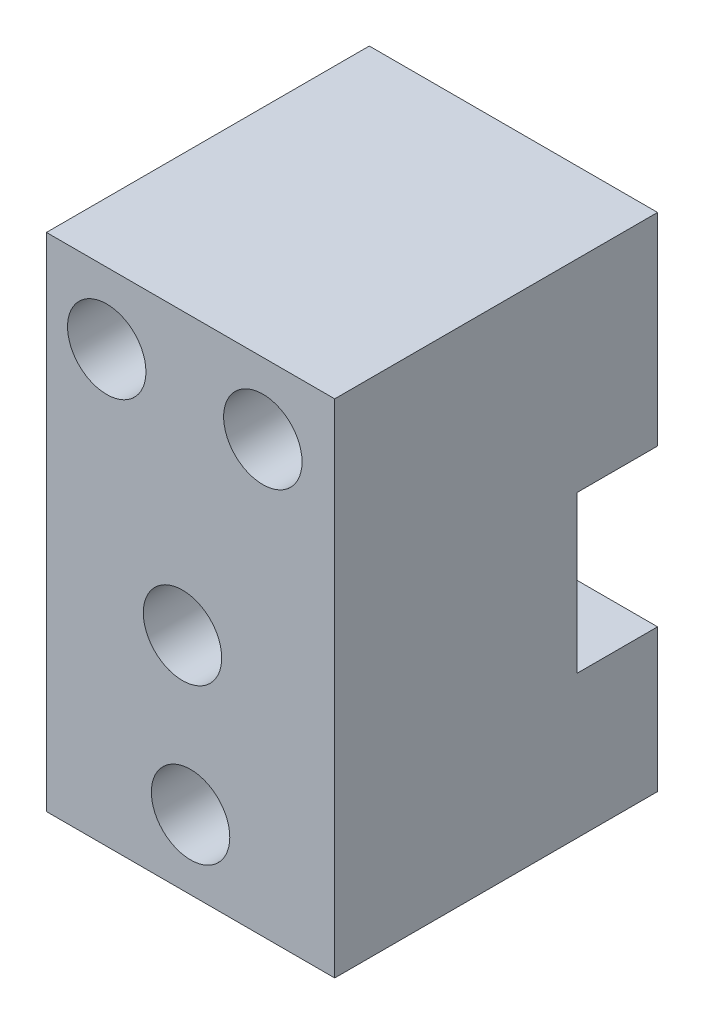
SolidWorks part; units mm, degrees
ref_plane "Plan de face" through (0, 0, 0) normal (0, 0, 1) x (1, 0, 0)
ref_plane "Plan de dessus" through (0, 0, 0) normal (0, 1, 0) x (1, 0, 0)
ref_plane "Plan de droite" through (0, 0, 0) normal (1, 0, 0) x (0, 0, -1)
sketch "Esquisse1" plane through (0, 0, 0) normal (0, 0, 1) x (1, 0, 0)
  line L1 (-6.25, -10.875) -> (6.25, -10.875)
  line L2 (-6.25, -10.875) -> (-6.25, 10.875)
  line L3 (-6.25, 10.875) -> (6.25, 10.875)
  line L4 (6.25, -10.875) -> (6.25, 10.875)
  line L5 (-6.25, -10.875) -> (6.25, 10.875) construction
  line L6 (-6.25, 10.875) -> (6.25, -10.875) construction
  point P0 (0, 0)
  dimension "D1" = 21.75
  dimension "D2" = 12.5
extrude "Boss.-Extru.3" add sketch "Esquisse1" along normal blind 14
sketch "Esquisse9" plane through (0, 0, 14) normal (0, 0, 1) x (1, 0, 0)
  line L0 (-3.6356, -4.6863) -> (-3.6356, 2.1017)
  line L1 (-3.6356, -4.6863) -> (6.9438, -4.6863)
  line L2 (-3.6356, 2.1017) -> (6.9438, 2.1017)
  line L3 (6.9438, -4.6863) -> (6.9438, 2.1017)
extrude "Enlèv. mat.-Extru.7" cut sketch "Esquisse9" against normal blind 3.5
hole_wizard "Dégagement M32" positions "Esquisse17" profile "Esquisse16" hole size "M3" standard "JIS" end condition through all
sketch "Esquisse17" plane through (0, 0, 14) normal (0, 0, 1) x (1, 0, 0)
  point P0 (-0.35, -1.3062)
sketch "Esquisse16" plane through (-0.35, -1.3062, 14) normal (1, 0, 0) x (0, -1, 0)
  line L0 (0, 0) -> (0, 14)
  line L1 (0, 14) -> (1.7, 14)
  line L2 (1.7, 14) -> (1.7, 0)
  line L5 (1.7, 0) -> (0, 0)
  line L11 (0, -6.35) -> (0, 107.95) construction
  dimension "Diamètre du perçage jusqu'au prochain" = 3.4
  dimension "Profondeur du perçage jusqu'au prochain" = 14
hole_wizard "Dégagement M33" positions "Esquisse20" profile "Esquisse18" hole size "M3" standard "JIS" end condition through all
sketch "Esquisse20" plane through (0, 0, 14) normal (0, 0, 1) x (1, 0, 0)
  point P0 (-3.6356, 7.7949)
  point P2 (3.1342, 7.7949)
  point P4 (0, -7.8658)
sketch "Esquisse18" plane through (-3.6356, 7.7949, 14) normal (1, 0, 0) x (0, -1, 0)
  line L0 (0, 0) -> (0, 14)
  line L1 (0, 14) -> (1.7, 14)
  line L2 (1.7, 14) -> (1.7, 0)
  line L5 (1.7, 0) -> (0, 0)
  line L11 (0, -6.35) -> (0, 107.95) construction
  dimension "Diamètre du perçage jusqu'au prochain" = 3.4
  dimension "Profondeur du perçage jusqu'au prochain" = 14
sketch "Esquisse21" plane through (6.25, 0, 0) normal (1, 0, 0) x (0, 0, -1)
  line L0 (-7, 10.875) -> (-7, -10.875) construction
  line L1 (-14, 10.875) -> (0, 10.875) construction
  line L2 (-14, -10.875) -> (0, -10.875) construction
ref_axis "Axe1" through (6.25, 10.875, 7) along (0, -1, 0)
ref_plane "Plan1" through (0, 0, 7) normal (0, 0, 1) x (0, -1, 0)
mirror "Symétrie1" about plane through (0, 0, 7) normal (0, 0, 1) of "Enlèv. mat.-Extru.7"
sketch "Esquisse23" plane through (0, 0, 10.5) normal (0, 0, 1) x (1, 0, 0)
  line L4 (-3.6356, 2.1017) -> (-3.6356, -4.6863)
  line L5 (6.25, 2.1017) -> (6.25, -4.6863)
  line L7 (6.25, -4.6863) -> (-3.6356, -4.6863)
  line L8 (-3.6356, -4.6863) -> (-3.6356, 2.1017)
  line L9 (-3.6356, 2.1017) -> (6.25, 2.1017)
  line L10 (6.25, -4.6863) -> (-3.6356, -4.6863)
  line L11 (-3.6356, -4.6863) -> (-3.6356, 2.1017)
  line L12 (-3.6356, 2.1017) -> (6.25, 2.1017)
  circle M4 centre (-0.35, -1.3062) radius 1.7
  line M5 (6.25, -4.6863) -> (6.25, 2.1017)
  line M6 (6.25, 2.1017) -> (-3.6356, 2.1017)
  line M7 (-3.6356, 2.1017) -> (-3.6356, -4.6863)
  line M8 (-3.6356, -4.6863) -> (6.25, -4.6863)
  dimension "D1" = 0
extrude "Boss.-Extru.4" add sketch "Esquisse23" along normal up to surface (3.5 mm away) contours M8 M5 M6 M7 M4 region at (1.5665, -1.2901, 10.5) up to face at (-1.9356, 7.7949, 14)
